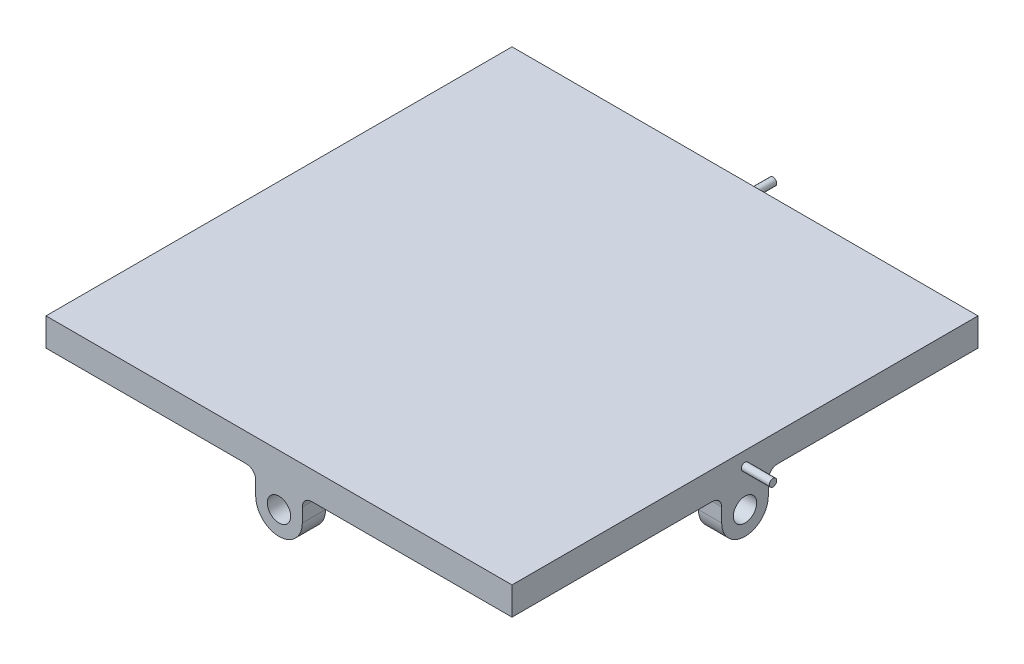
SolidWorks part; units mm, degrees
ref_plane "Plano frontal" through (0, 0, 0) normal (0, 0, 1) x (1, 0, 0)
ref_plane "Plano superior" through (0, 0, 0) normal (0, 1, 0) x (1, 0, 0)
ref_plane "Plano direito" through (0, 0, 0) normal (1, 0, 0) x (0, 0, -1)
sketch "Esboço1" plane through (0, 0, 0) normal (0, 1, 0) x (1, 0, 0)
  line L1 (0, 0) -> (500, 0)
  line L2 (0, 0) -> (0, 500)
  line L3 (0, 500) -> (500, 500)
  line L4 (500, 0) -> (500, 500)
  dimension "D1" = 500
extrude "Ressalto-extrusão1" add sketch "Esboço1" along normal blind 30
sketch "Esboço2" plane through (0, 0, 0) normal (0, -1, 0) x (1, 0, 0)
  line L0 (0, -500) -> (0, 0) construction
  line L1 (225, -25) -> (275, -25)
  line L2 (225, -25) -> (225, 0)
  line L3 (225, 0) -> (275, 0)
  line L4 (275, -25) -> (275, 0)
  line L5 (0, 0) -> (500, 0) construction
  line L6 (500, 0) -> (500, -500) construction
  line L7 (475, -225) -> (500, -225)
  line L9 (500, -500) -> (0, -500) construction
  line L14 (475, -225) -> (475, -275)
  line L15 (475, -275) -> (500, -275)
  line L16 (500, -225) -> (500, -275)
  line L22 (0, -225) -> (0, -275)
  line L23 (25, -275) -> (0, -275)
  line L24 (25, -225) -> (25, -275)
  line L25 (25, -225) -> (0, -225)
  line L26 (275, -475) -> (275, -500)
  line L27 (225, -500) -> (275, -500)
  line L28 (225, -475) -> (225, -500)
  line L29 (225, -475) -> (275, -475)
  point P6 (250, 0)
  point P21 (500, -250)
  dimension "D1" = 250
  dimension "D2" = 50
  dimension "D3" = 25
  dimension "D4" = 0
  dimension "D5" = 250
  dimension "D6" = 50
  dimension "D7" = 25
  dimension "D8" = 0
extrude "Ressalto-extrusão2" add sketch "Esboço2" along normal blind 50
sketch "Esboço3" plane through (0, 0, 0) normal (-1, 0, 0) x (0, 0, 1)
  line L3 (-225, -50) -> (-275, -50) construction
  line L4 (-275, -50) -> (-275, 0) construction
  circle A0 centre (-250, -25) radius 12.5
  dimension "D3" = 25
  dimension "D1" = 25
  dimension "D2" = 25
extrude "Corte-extrusão1" cut sketch "Esboço3" against normal through all
sketch "Esboço4" plane through (0, 0, 0) normal (0, 0, 1) x (1, 0, 0)
  line L0 (275, -50) -> (275, 0) construction
  line L1 (0, 0) -> (225, 0) construction
  circle A0 centre (250, -25) radius 12.5
  dimension "D3" = 25
  dimension "D1" = 25
  dimension "D2" = 25
extrude "Corte-extrusão2" cut sketch "Esboço4" against normal through all
fillet "Filete1" radius 25 8 edges at (275, -50, -487.5) (225, -50, -487.5) (12.5, -50, -275) (12.5, -50, -225) (487.5, -50, -275) (487.5, -50, -225) (275, -50, -12.5) (225, -50, -12.5)
fillet "Filete4" radius 10 8 edges at (487.5, 0, -275) (487.5, 0, -225) (275, 0, -12.5) (225, 0, -12.5) (12.5, 0, -225) (275, 0, -487.5) (225, 0, -487.5) (12.5, 0, -275)
sketch "Esboço5" plane through (0, 0, 0) normal (0, -1, 0) x (1, 0, 0)
  line L0 (25, -285) -> (25, -215) construction
  line L1 (50, -25) -> (450, -25)
  line L2 (25, -50) -> (25, -450)
  line L3 (50, -475) -> (450, -475)
  line L4 (475, -50) -> (475, -450)
  line L6 (215, -25) -> (285, -25) construction
  line L7 (475, -215) -> (475, -285) construction
  line L8 (285, -475) -> (215, -475) construction
  line L9 (25, -450) -> (50, -475)
  line L10 (450, -475) -> (475, -450)
  line L11 (25, -50) -> (50, -25)
  line L12 (450, -25) -> (475, -50)
  point P0 (25, -25)
  point P1 (475, -475)
  point P2 (25, -475)
  point P3 (475, -25)
extrude "Corte-extrusão3" cut sketch "Esboço5" against normal blind 15
sketch "Esboço6" plane through (500, 0, 0) normal (1, 0, 0) x (0, 0, -1)
  line L0 (250, 30) -> (250, -50) construction
  line L1 (0, 15) -> (500, 15) construction
  line L3 (0, 30) -> (500, 30) construction
  line L4 (0, 30) -> (0, 0) construction
  line L5 (500, 30) -> (500, 0) construction
  circle A0 centre (250, 15) radius 4
  point P6 (0, 0)
  point P7 (0, 0)
  point P8 (0, 0)
  point P9 (250, 30)
  point P12 (250.2734, -55.3831)
  point P13 (250, -50)
  point P15 (0, 15)
  point P18 (500, 15)
  point P21 (0, 0)
  dimension "D1" = 8
extrude "Ressalto-extrusão3" add sketch "Esboço6" along normal blind 30
sketch "Esboço7" plane through (0, 0, -500) normal (0, 0, -1) x (-1, 0, 0)
  line L0 (-250, 30) -> (-250, -50) construction
  line L1 (-500, 30) -> (0, 30) construction
  line L2 (-500, 15) -> (0, 15) construction
  line L3 (-500, 30) -> (-500, 0) construction
  line L4 (0, 30) -> (0, 0) construction
  circle A0 centre (-250, 15) radius 4
  dimension "D1" = 8
extrude "Ressalto-extrusão4" add sketch "Esboço7" along normal blind 30
